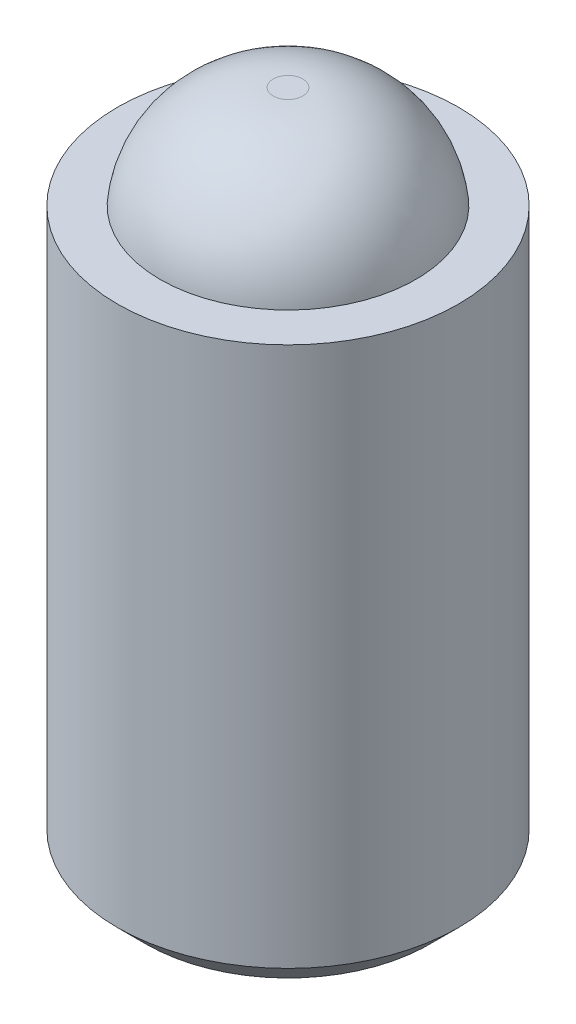
SolidWorks part; units mm, degrees
ref_plane "前视基准面" through (0, 0, 0) normal (0, 0, 1) x (1, 0, 0)
ref_plane "上视基准面" through (0, 0, 0) normal (0, 1, 0) x (1, 0, 0)
ref_plane "右视基准面" through (0, 0, 0) normal (1, 0, 0) x (0, 0, -1)
sketch "草图1" plane through (0, 0, 0) normal (0, 1, 0) x (1, 0, 0)
  circle A0 centre (0, 0) radius 3
  dimension "D1" = 6
extrude "凸台-拉伸1" add sketch "草图1" along normal blind 10
sketch "草图2" plane through (0, 10, 0) normal (0, 1, 0) x (1, 0, 0)
  circle A0 centre (0, 0) radius 2.25
  dimension "D1" = 4.5
extrude "凸台-拉伸2" add sketch "草图2" along normal blind 1.8
fillet "圆角2" radius 2 1 edges at (0, 11.8, 2.25)
chamfer "倒角1" distance 0.5 angle 45 1 edges at (0, 0, 3)
sketch "草图3" plane through (0, 0, 0) normal (0, -1, 0) x (1, 0, 0)
  line L1 (0, 1.8088) -> (-1.5664, 0.9044)
  line L2 (-1.5664, 0.9044) -> (-1.5664, -0.9044)
  line L3 (-1.5664, -0.9044) -> (0, -1.8088)
  line L4 (0, -1.8088) -> (1.5664, -0.9044)
  line L5 (1.5664, -0.9044) -> (1.5664, 0.9044)
  line L6 (1.5664, 0.9044) -> (0, 1.8088)
  circle A0 centre (0, 0) radius 1.5664 construction
extrude "切除-拉伸1" cut sketch "草图3" against normal blind 1.8
